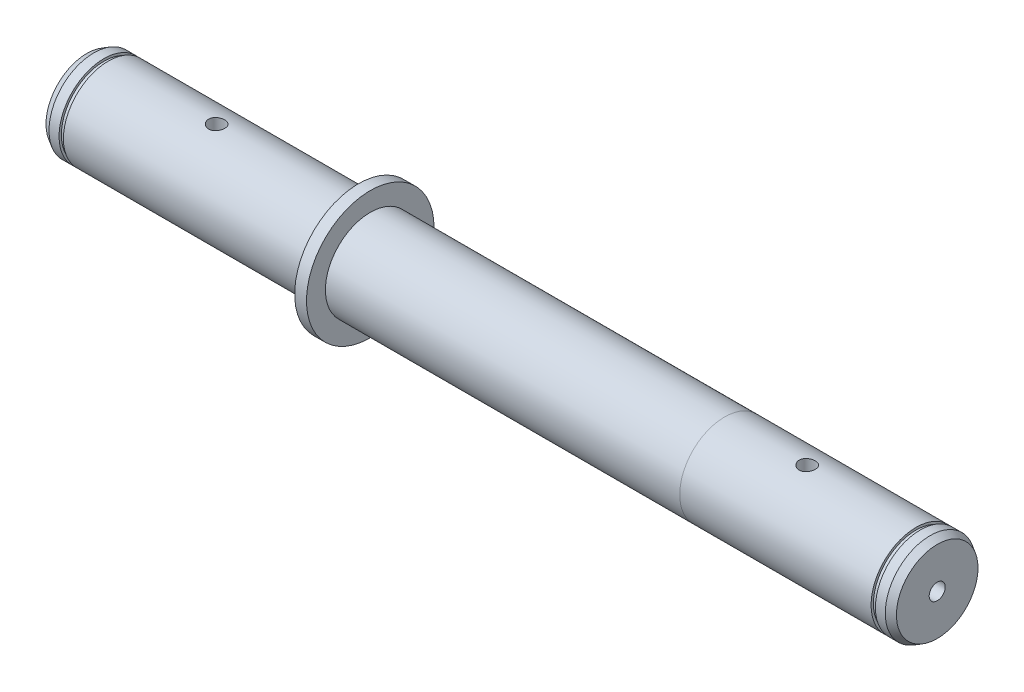
SolidWorks part; units mm, degrees
material "1.7225 (42CrMo4)"
ref_plane "E_Oben" through (0, 0, 0) normal (0, 0, 1) x (1, 0, 0)
ref_plane "E_Vorne" through (0, 0, 0) normal (0, 1, 0) x (1, 0, 0)
ref_plane "E_Rechts" through (0, 0, 0) normal (1, 0, 0) x (0, 0, -1)
ref_axis "A_Drehachse" through (-88.99, 0, 0) along (1, 0, 0)
sketch "Skizze1" plane through (0, 0, 0) normal (0, 0, 1) x (1, 0, 0)
  line L1 (0, -55) -> (0, 55) construction
  line L3 (180, 19) -> (180, 0)
  line L4 (180, 0) -> (-180, 0)
  line L7 (-180, 19) -> (-180, 0)
  line L10 (-65, 19) -> (-65, 27)
  line L11 (-65, 27) -> (-60, 27)
  line L12 (-60, 27) -> (-60, 19.0001)
  line L13 (-180, 19) -> (-65, 19)
  line L14 (-60, 19.0001) -> (90, 19.0001)
  line L15 (90, 19.0001) -> (90, 19)
  line L16 (90, 19) -> (180, 19)
  point P12 (0, 0)
  point P19 (-62.5, 27)
  dimension "D1" = 19.0001
  dimension "D2" = 19
  dimension "D3" = 19
  dimension "D4" = 360
  dimension "D5" = 115
  dimension "D6" = 5
  dimension "D7" = 27
  dimension "D8" = 150
revolve "Rotation1" add sketch "Skizze1" angle 360 about L4
hole_wizard "M8 Tapped Hole1" positions "Skizze13" profile "Skizze14" tap size "M8" standard "DIN"
sketch "Skizze13" plane through (180, 0, 0) normal (1, 0, 0) x (0, 0, -1)
  point P0 (0, 0)
  point P3 (0, 0)
sketch "Skizze14" plane through (180, 0, 0) normal (0, 1, 0) x (0, 0, -1)
  line L0 (0, 0) -> (0, 67.0429)
  line L1 (0, 67.0429) -> (3.4, 65)
  line L2 (3.4, 65) -> (3.4, 0)
  line L5 (3.4, 0) -> (0, 0)
  line L10 (0, 67.0429) -> (-3.4, 65) construction
  line L11 (0, -6.35) -> (0, 107.95) construction
  dimension "Bohrerdurchmesser" = 6.8
  dimension "Bohrungstiefe" = 65
  dimension "Spitzenwinkel" = 118
cosmetic thread "Bohrungsgewinde2" parameters "D1"=20, "D2"=8
hole_wizard "M8 Gewindebohrung3" positions "Skizze17" profile "Skizze18" tap size "M8" standard "DIN" end condition through all
sketch "Skizze17" plane through (0, 0, 0) normal (0, 1, 0) x (1, 0, 0)
  line L0 (-29.7, 0) -> (29.7, 0) construction
  line L1 (-88.99, 0) -> (88.99, 0) construction
  line L3 (180, -19) -> (180, 19) construction
  point P0 (-125, 0)
  point P4 (125, 0)
  dimension "D3" = 305
  dimension "D4" = 55
sketch "Skizze18" plane through (-125, 0, 0) normal (1, 0, 0) x (0, 0, -1)
  line L0 (0, 0) -> (0, 27)
  line L1 (0, 27) -> (3.4, 27)
  line L2 (3.4, 27) -> (3.4, 0)
  line L5 (3.4, 0) -> (0, 0)
  line L11 (0, -6.35) -> (0, 107.95) construction
  dimension "Bohrerdurchmesser" = 6.8
  dimension "Bohrungstiefe" = 27
mirror "Spiegeln2" about plane through (0, 0, 0) normal (0, 1, 0) of "M8 Gewindebohrung3"
sketch "Skizze19" plane through (0, 0, 0) normal (0, 0, 1) x (1, 0, 0)
  line L8 (180, 19) -> (128.4, 19) construction
  line L9 (171, 19) -> (172.85, 19)
  line L10 (171, 19) -> (171, 18)
  line L11 (171, 18) -> (172.85, 18)
  line L12 (172.85, 19) -> (172.85, 18)
  line L13 (180, -19) -> (180, 19) construction
  dimension "D1" = 7.15
  dimension "D2" = 1
  dimension "D4" = 1.85
revolve "Schnitt-Rotation1" cut sketch "Skizze19" angle 360 about axis through (-88.99, 0, 0) along (1, 0, 0)
sketch "Skizze20" plane through (0, 0, 0) normal (0, 0, 1) x (1, 0, 0)
  line L9 (-128.3999, 19) -> (-180, 19) construction
  line L10 (-180, 19) -> (-180, -19) construction
  line L11 (-172.75, 19) -> (-170.9, 19)
  line L12 (-172.75, 19) -> (-172.75, 18)
  line L13 (-172.75, 18) -> (-170.9, 18)
  line L14 (-170.9, 19) -> (-170.9, 18)
  dimension "D1" = 7.25
  dimension "D4" = 1
  dimension "D5" = 1.85
revolve "Schnitt-Rotation2" cut sketch "Skizze20" angle 360 about axis through (-88.99, 0, 0) along (1, 0, 0)
sketch "Sketch3" plane through (-180, 0, 0) normal (-1, 0, 0) x (0, 0, 1)
  point P0 (0, 0)
hole_wizard "M8 Tapped Hole2" positions "Sketch3" profile "Sketch2" tap size "M8" standard "DIN"
sketch "Sketch2" plane through (-180, 0, 0) normal (0, 1, 0) x (0, 0, 1)
  line L0 (0, 0) -> (0, 67.0429)
  line L1 (0, 67.0429) -> (3.4, 65)
  line L2 (3.4, 65) -> (3.4, 0)
  line L5 (3.4, 0) -> (0, 0)
  line L10 (0, 67.0429) -> (-3.4, 65) construction
  line L11 (0, -6.35) -> (0, 107.95) construction
  dimension "Tap Drill Dia." = 6.8
  dimension "Tap Drill Depth" = 65
  dimension "Drill Angle" = 118
cosmetic thread "Hole Thread1" parameters "D1"=20, "D2"=8
chamfer "Fase1" distance 3 angle 30 2 edges at (180, 0, -19) (-180, 0, -19) first distance on face at (180, 0, -19) first distance on face at (-180, 0, -19)
